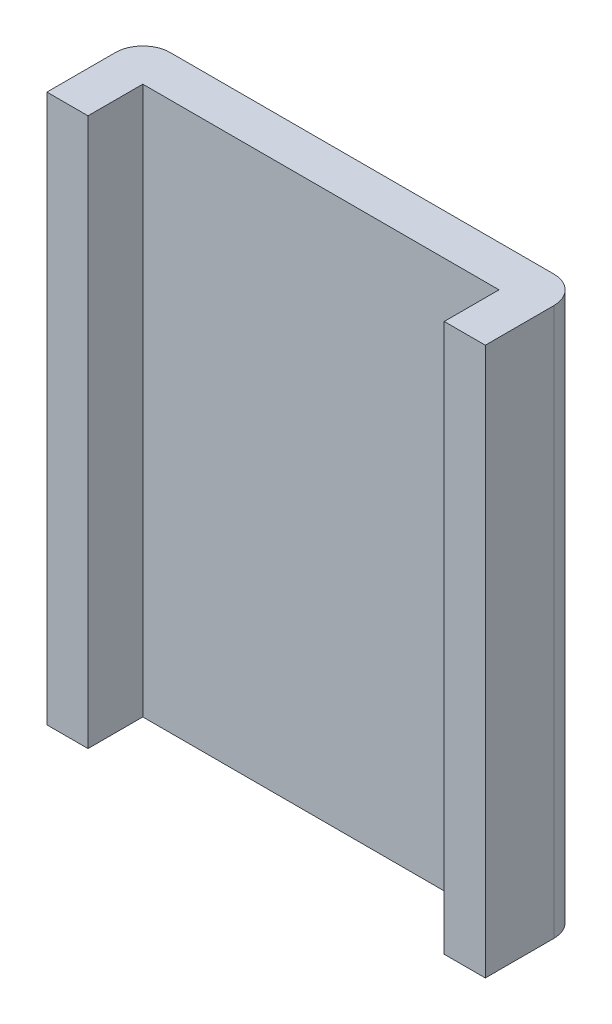
SolidWorks part; units mm, degrees
ref_plane "Front Plane" through (0, 0, 0) normal (0, 0, 1) x (1, 0, 0)
ref_plane "Top Plane" through (0, 0, 0) normal (0, 1, 0) x (1, 0, 0)
ref_plane "Right Plane" through (0, 0, 0) normal (1, 0, 0) x (0, 0, -1)
sketch "Sketch1" plane through (0, 0, 0) normal (0, 0, 1) x (1, 0, 0)
  line L1 (-4, 5) -> (4, 5)
  line L2 (-4, 5) -> (-4, -5)
  line L3 (-4, -5) -> (4, -5)
  line L4 (4, 5) -> (4, -5)
  line L5 (-4, 5) -> (4, -5) construction
  line L6 (-4, -5) -> (4, 5) construction
  line L7 (-3.25, 5) -> (3.25, 5)
  line L8 (-3.25, 5) -> (-3.25, -5)
  line L9 (-3.25, -5) -> (3.25, -5)
  line L10 (3.25, 5) -> (3.25, -5)
  line L11 (-3.25, 5) -> (3.25, -5) construction
  line L12 (-3.25, -5) -> (3.25, 5) construction
  point P0 (0, 0)
  point P6 (0, 0)
  dimension "D1" = 8
  dimension "D2" = 10
  dimension "D3" = 10
  dimension "D4" = 6.5
extrude "Boss-Extrude1" add sketch "Sketch1" along normal blind 0.75 contours L10 L1 L8 L3 region at (0, 0, 0)
extrude "Boss-Extrude2" add sketch "Sketch1<3>" along normal blind 1.75 contours L1 L10 L3 L4 | L8 L1 L2 L3 region at (-3.625, 0, 0) region at (3.625, 0, 0)
sketch "Sketch1<3>" plane through (0, 0, 0) normal (0, 0, 1) x (1, 0, 0) same geometry as "Sketch1"
ref_axis "Axis1" through (0, 0, -4.7229) along (0, 0, 1)
ref_plane "Plane1" through (0, 0, 0) normal (0.9659, 0.2588, 0) x (0, 0, 1)
ref_plane "Plane2" through (0, 0, 0) normal (0.9659, -0.2588, 0) x (0, 0, 1)
fillet "Fillet1" radius 0.5 2 edges at (-4, 0, 0) (4, 0, 0)
equation "\"D3@Sketch1\"=\"D2@Sketch1\""
equation "\"D1@Sketch1\"=\"D4@Sketch1\"+1.5"
